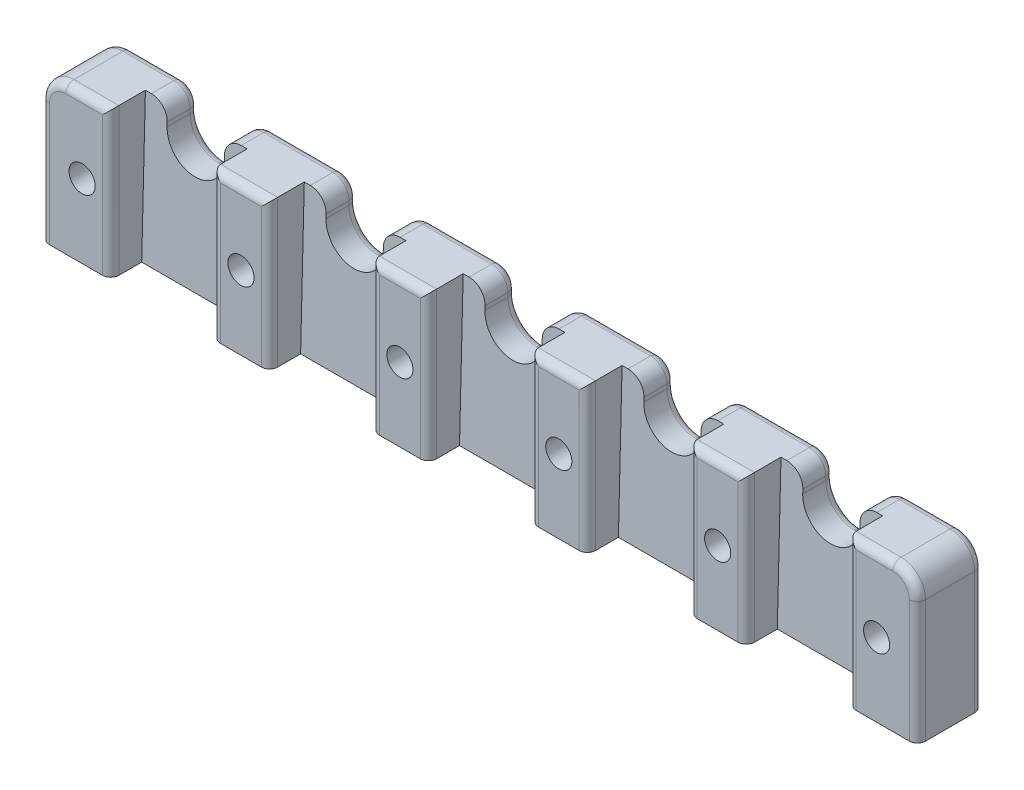
SolidWorks part; units mm, degrees
ref_plane "Front Plane" through (0, 0, 0) normal (0, 0, 1) x (1, 0, 0)
ref_plane "Top Plane" through (0, 0, 0) normal (0, 1, 0) x (1, 0, 0)
ref_plane "Right Plane" through (0, 0, 0) normal (1, 0, 0) x (0, 0, -1)
sketch "Sketch1" plane through (0, 0, 0) normal (0, 1, 0) x (1, 0, 0)
  line L0 (0, 0) -> (-0.0507, 0) construction
  line L1 (19.45, 0) -> (19.3993, 0) construction
  line L2 (-6.225, 10.725) -> (6.225, 10.725)
  line L3 (-6.225, 10.725) -> (-6.225, -10.725)
  line L4 (-6.225, -10.725) -> (6.225, -10.725)
  line L5 (6.225, 10.725) -> (6.225, -10.725)
  line L6 (-6.225, 10.725) -> (6.225, -10.725) construction
  line L7 (-6.225, -10.725) -> (6.225, 10.725) construction
  line L8 (13.225, 10.725) -> (13.225, -10.725)
  line L9 (13.225, 10.725) -> (25.675, 10.725)
  line L10 (25.675, 10.725) -> (25.675, -10.725)
  line L11 (13.225, -10.725) -> (25.675, -10.725)
  line L12 (38.9, 0) -> (38.8493, 0) construction
  line L13 (32.675, 10.725) -> (32.675, -10.725)
  line L14 (32.675, 10.725) -> (45.125, 10.725)
  line L15 (45.125, 10.725) -> (45.125, -10.725)
  line L16 (32.675, -10.725) -> (45.125, -10.725)
  line L17 (58.35, 0) -> (58.2993, 0) construction
  line L18 (52.125, 10.725) -> (52.125, -10.725)
  line L19 (52.125, 10.725) -> (64.575, 10.725)
  line L20 (64.575, 10.725) -> (64.575, -10.725)
  line L21 (52.125, -10.725) -> (64.575, -10.725)
  line L22 (77.8, 0) -> (77.7493, 0) construction
  line L23 (71.575, 10.725) -> (71.575, -10.725)
  line L24 (71.575, 10.725) -> (84.025, 10.725)
  line L25 (84.025, 10.725) -> (84.025, -10.725)
  line L26 (71.575, -10.725) -> (84.025, -10.725)
  line L27 (-19.225, -19.625) -> (-5.1, -19.625)
  line L28 (-9.225, 13.725) -> (87.025, 13.725)
  line L29 (-9.225, 13.725) -> (-9.225, -10.725)
  line L30 (-5.1, -13.725) -> (5.1, -13.725)
  line L31 (87.025, 13.725) -> (87.025, -10.725)
  line L32 (-9.225, 13.725) -> (87.025, -13.725) construction
  line L33 (-9.225, -13.725) -> (87.025, 13.725) construction
  line L34 (-19.225, -19.625) -> (-19.225, -10.725)
  line L35 (-19.225, -10.725) -> (-9.225, -10.725)
  line L36 (87.025, -10.725) -> (97.025, -10.725)
  line L37 (97.025, -10.725) -> (97.025, -19.625)
  line L38 (-5.1, -13.725) -> (-5.1, -19.625)
  line L39 (5.1, -13.725) -> (5.1, -19.625)
  line L40 (5.1, -19.625) -> (14.35, -19.625)
  line L41 (14.35, -19.625) -> (14.35, -13.725)
  line L42 (24.55, -13.725) -> (24.55, -19.625)
  line L43 (24.55, -19.625) -> (33.8, -19.625)
  line L44 (33.8, -19.625) -> (33.8, -13.725)
  line L45 (44, -13.725) -> (44, -19.625)
  line L46 (44, -19.625) -> (53.25, -19.625)
  line L47 (53.25, -19.625) -> (53.25, -13.725)
  line L48 (63.45, -13.725) -> (63.45, -19.625)
  line L49 (63.45, -19.625) -> (72.7, -19.625)
  line L50 (72.7, -19.625) -> (72.7, -13.725)
  line L51 (82.9, -13.725) -> (82.9, -19.625)
  line L52 (5.1, -19.625) -> (14.35, -19.625)
  line L53 (24.55, -19.625) -> (33.8, -19.625)
  line L54 (44, -19.625) -> (53.25, -19.625)
  line L55 (63.45, -19.625) -> (72.7, -19.625)
  line L56 (82.9, -19.625) -> (97.025, -19.625)
  line L57 (14.35, -13.725) -> (24.55, -13.725)
  line L58 (33.8, -13.725) -> (44, -13.725)
  line L59 (53.25, -13.725) -> (63.45, -13.725)
  line L60 (72.7, -13.725) -> (82.9, -13.725)
  line L61 (72.7, -13.725) -> (72.7, -19.625)
  line L62 (63.45, -19.625) -> (63.45, -13.725)
  line L63 (53.25, -13.725) -> (53.25, -19.625)
  line L64 (44, -19.625) -> (44, -13.725)
  line L65 (0, -10.725) -> (0, -17.5719) construction
  line L66 (19.45, -10.725) -> (19.45, -16.6206) construction
  line L67 (38.9, -10.725) -> (38.9, -17.5719) construction
  line L68 (58.35, -10.725) -> (58.35, -17.5719) construction
  line L69 (77.8, -10.725) -> (77.8, -17.5719) construction
  point P71 (0, -13.725)
  point P72 (19.45, -13.725)
  point P73 (38.9, -13.725)
  point P74 (58.35, -13.725)
  point P75 (77.8, -13.725)
  dimension "D1" = 12.45
  dimension "D2" = 21.45
  dimension "D4" = 3
  dimension "D5" = 3
  dimension "D6" = 5.9
  dimension "D7" = 10
  dimension "D8" = 10
  dimension "D9" = 10.2
  dimension "D10" = 10.2
  dimension "D11" = 10.2
  dimension "D12" = 10.2
  dimension "D13" = 10.2
  dimension "D3" = 5
extrude "Boss-Extrude1" add sketch "Sketch1" along normal blind 18 contours L50 L60 L51 L56 L37 L36 L31 L28 L29 L35 L34 L27 L38 L30 L39 L40 L41 L57 L42 L43 L44 L58 L45 L46 L47 L59 L48 L49 L2 L5 L4 L3 L11 L8 L9 L10 L16 L13 L14 L15 L21 L18 L19 L20 L26 L23
sketch "Sketch2" plane through (0, 18, 0) normal (0, 1, 0) x (1, 0, 0)
  line L0 (-9.225, 13.725) -> (-9.225, -10.725) construction
  line L1 (-19.225, -10.725) -> (-9.225, -10.725)
  line L2 (-19.225, -10.725) -> (-19.225, -7.725)
  line L3 (-19.225, -7.725) -> (-9.225, -7.725)
  line L4 (-9.225, -10.725) -> (-9.225, -7.725)
  line L5 (87.025, 13.725) -> (87.025, -10.725) construction
  line L6 (97.025, -10.725) -> (87.025, -10.725)
  line L7 (97.025, -10.725) -> (97.025, -7.725)
  line L8 (97.025, -7.725) -> (87.025, -7.725)
  line L9 (87.025, -10.725) -> (87.025, -7.725)
  dimension "D1" = 3
  dimension "D2" = 3
extrude "Boss-Extrude2" add sketch "Sketch2" against normal up to surface (18 mm away) up to face at (0, 0, 0)
sketch "Sketch4" plane through (0, 18, 0) normal (0, 1, 0) x (1, 0, 0)
  line L0 (-6.225, 10.725) -> (6.225, 10.725) construction
  line L1 (-3.5, 14.8177) -> (3.5, 14.8177)
  line L2 (-3.5, 14.8177) -> (-3.5, 6.6323)
  line L3 (-3.5, 6.6323) -> (3.5, 6.6323)
  line L4 (3.5, 14.8177) -> (3.5, 6.6323)
  line L5 (-3.5, 14.8177) -> (3.5, 6.6323) construction
  line L6 (-3.5, 6.6323) -> (3.5, 14.8177) construction
  line L7 (13.225, 10.725) -> (25.675, 10.725) construction
  line L8 (15.95, 15.2856) -> (22.95, 15.2856)
  line L9 (15.95, 15.2856) -> (15.95, 6.1644)
  line L10 (15.95, 6.1644) -> (22.95, 6.1644)
  line L11 (22.95, 15.2856) -> (22.95, 6.1644)
  line L12 (15.95, 15.2856) -> (22.95, 6.1644) construction
  line L13 (15.95, 6.1644) -> (22.95, 15.2856) construction
  line L14 (32.675, 10.725) -> (45.125, 10.725) construction
  line L15 (35.4, 17.4328) -> (42.4, 17.4328)
  line L16 (35.4, 17.4328) -> (35.4, 4.0172)
  line L17 (35.4, 4.0172) -> (42.4, 4.0172)
  line L18 (42.4, 17.4328) -> (42.4, 4.0172)
  line L19 (35.4, 17.4328) -> (42.4, 4.0172) construction
  line L20 (35.4, 4.0172) -> (42.4, 17.4328) construction
  line L21 (52.125, 10.725) -> (64.575, 10.725) construction
  line L22 (54.85, 15.7825) -> (61.85, 15.7825)
  line L23 (54.85, 15.7825) -> (54.85, 5.6675)
  line L24 (54.85, 5.6675) -> (61.85, 5.6675)
  line L25 (61.85, 15.7825) -> (61.85, 5.6675)
  line L26 (54.85, 15.7825) -> (61.85, 5.6675) construction
  line L27 (54.85, 5.6675) -> (61.85, 15.7825) construction
  line L28 (71.575, 10.725) -> (84.025, 10.725) construction
  line L29 (74.3, 15.0129) -> (81.3, 15.0129)
  line L30 (74.3, 15.0129) -> (74.3, 6.4371)
  line L31 (74.3, 6.4371) -> (81.3, 6.4371)
  line L32 (81.3, 15.0129) -> (81.3, 6.4371)
  line L33 (74.3, 15.0129) -> (81.3, 6.4371) construction
  line L34 (74.3, 6.4371) -> (81.3, 15.0129) construction
  point P0 (0, 10.725)
  point P7 (19.45, 10.725)
  point P14 (38.9, 10.725)
  point P21 (58.35, 10.725)
  point P28 (77.8, 10.725)
  dimension "D1" = 7
  dimension "D2" = 7
  dimension "D3" = 7
  dimension "D4" = 7
  dimension "D5" = 7
extrude "Cut-Extrude2" cut sketch "Sketch4" against normal blind 6
fillet "Fillet3" radius 3.5 10 edges at (81.3, 12, -12.225) (74.3, 12, -12.225) (54.85, 12, -12.225) (61.85, 12, -12.225) (42.4, 12, -12.225) (35.4, 12, -12.225) (15.95, 12, -12.225) (22.95, 12, -12.225) (3.5, 12, -12.225) (-3.5, 12, -12.225)
fillet "Fillet4" radius 2 10 edges at (35.4, 18, -12.225) (54.85, 18, -12.225) (74.3, 18, -12.225) (81.3, 18, -12.225) (61.85, 18, -12.225) (42.4, 18, -12.225) (22.95, 18, -12.225) (15.95, 18, -12.225) (3.5, 18, -12.225) (-3.5, 18, -12.225)
sketch "Sketch5" plane through (0, 0, 19.625) normal (0, 0, 1) x (1, 0, 0)
  line L0 (-19.225, 9) -> (97.025, 9) construction
  line L1 (-19.225, 18) -> (-19.225, 0) construction
  line L2 (97.025, 18) -> (97.025, 0) construction
  line L3 (5.1, 9) -> (14.35, 9) construction
  line L4 (5.1, 18) -> (5.1, 0) construction
  line L5 (14.35, 18) -> (14.35, 0) construction
  line L6 (24.55, 9) -> (33.8, 9) construction
  line L7 (24.55, 18) -> (24.55, 0) construction
  line L8 (33.8, 18) -> (33.8, 0) construction
  line L9 (44, 9) -> (53.25, 9) construction
  line L10 (44, 18) -> (44, 0) construction
  line L11 (53.25, 18) -> (53.25, 0) construction
  line L12 (63.45, 9) -> (72.7, 9) construction
  line L13 (63.45, 18) -> (63.45, 0) construction
  line L14 (72.7, 18) -> (72.7, 0) construction
  line L15 (-5.1, 18) -> (-5.1, 0) construction
  line L16 (82.9, 18) -> (82.9, 0) construction
  circle A0 centre (9.725, 9) radius 1.6
  circle A1 centre (29.175, 9) radius 1.6
  circle A2 centre (48.625, 9) radius 1.6
  circle A3 centre (68.075, 9) radius 1.6
  circle A4 centre (87.53, 9) radius 1.6
  circle A5 centre (-9.73, 9) radius 1.6
  dimension "D1" = 3.2
  dimension "D2" = 3.2
  dimension "D3" = 3.2
  dimension "D4" = 3.2
  dimension "D5" = 3.2
  dimension "D6" = 3.2
  dimension "D7" = 4.63
  dimension "D8" = 4.63
extrude "Cut-Extrude3" cut sketch "Sketch5" against normal through all
sketch "Sketch7" plane through (0, 0, -13.725) normal (0, 0, -1) x (-1, 0, 0)
  line L0 (-87.53, 9) -> (-92.53, 9) construction
  line L1 (9.73, 9) -> (14.73, 9) construction
  line L2 (-92.53, 9) -> (-92.53, -2.9346)
  line L3 (-92.53, -2.9346) -> (-102.871, -2.9346)
  line L4 (-102.871, -2.9346) -> (-102.871, 21.3195)
  line L5 (-102.871, 21.3195) -> (-92.53, 21.3195)
  line L6 (-92.53, 21.3195) -> (-92.53, 9)
  line L7 (14.73, 9) -> (14.73, -3.3373)
  line L8 (14.73, -3.3373) -> (26.9404, -3.3373)
  line L9 (26.9404, -3.3373) -> (26.9404, 20.1807)
  line L10 (26.9404, 20.1807) -> (14.73, 20.1807)
  line L11 (14.73, 20.1807) -> (14.73, 9)
  dimension "D1" = 5
  dimension "D2" = 5
extrude "Cut-Extrude4" cut sketch "Sketch7" against normal through all
sketch "Sketch10" plane through (0, 0, 7.725) normal (0, 0, -1) x (-1, 0, 0)
  line L0 (-83.3, 18) -> (-87.025, 18) construction
  line L1 (-85.1625, 18) -> (-92.53, 18)
  line L2 (-85.1625, 18) -> (-85.1625, 0)
  line L3 (-85.1625, 0) -> (-92.53, 0)
  line L4 (-92.53, 18) -> (-92.53, 0)
  line L5 (9.225, 18) -> (5.5, 18) construction
  line L6 (14.73, 0) -> (7.3625, 0)
  line L7 (14.73, 0) -> (14.73, 18)
  line L8 (14.73, 18) -> (7.3625, 18)
  line L9 (7.3625, 0) -> (7.3625, 18)
  circle A0 centre (-87.53, 9) radius 1.6
  circle A1 centre (9.73, 9) radius 1.6
extrude "Boss-Extrude4" add sketch "Sketch10" along normal up to surface (21.45 mm away) up to face at (38.9, 14.5091, -13.725)
fillet "Fillet6" radius 3 2 edges at (-14.73, 18, 2.95) (92.53, 18, 2.95)
sketch "Sketch11" plane through (0, 18, 0) normal (0, 1, 0) x (1, 0, 0)
  line L1 (-18.1321, 4.725) -> (96.0074, 4.725)
  line L2 (-18.1321, 4.725) -> (-18.1321, 5.725)
  line L3 (-18.1321, 5.725) -> (96.0074, 5.725)
  line L4 (96.0074, 4.725) -> (96.0074, 5.725)
  line L5 (-11.73, 13.725) -> (-5.5, 13.725) construction
  dimension "D1" = 8
  dimension "D2" = 1
extrude "Cut-Extrude5" cut sketch "Sketch11" against normal through all
chamfer "Chamfer2" distance 1 angle 45 44 edges at (-9.915, 0, 19.625) (-14.73, 0, 7.45) (68.075, 0, 19.625) (63.45, 0, 16.675) (58.35, 0, 13.725) (53.25, 0, 16.675) (48.625, 0, 19.625) (44, 0, 16.675) (38.9, 0, 13.725) (33.8, 0, 16.675) (29.175, 0, 19.625) (24.55, 0, 16.675) (19.45, 0, 13.725) (14.35, 0, 16.675) (9.725, 0, 19.625) (5.1, 0, 16.675) (0, 0, 13.725) (-5.1, 0, 16.675) (92.53, 0, 7.45) (-6.225, 0, 3) (6.225, 0, 3) (25.675, 0, 3) (87.715, 0, 19.625) (13.225, 0, 3) (45.125, 0, 3) (32.675, 0, 3) (64.575, 0, 3) (52.125, 0, 3) (84.025, 0, 3) (71.575, 0, 3) (82.9, 0, 16.675) (77.8, 0, 13.725) (72.7, 0, 16.675) (77.8, 0, 10.725) (9.725, 0, -4.725) (88.2775, 0, -4.725) (68.075, 0, -4.725) (48.625, 0, -4.725) (29.175, 0, -4.725) (-10.4775, 0, -4.725) (58.35, 0, 10.725) (38.9, 0, 10.725) (19.45, 0, 10.725) (0, 0, 10.725)
fillet "Fillet7" radius 1 20 edges at (91.6513, 17.1213, -4.725) (71.575, 9.5, -4.725) (52.125, 9.5, -4.725) (32.675, 9.5, -4.725) (13.225, 9.5, -4.725) (6.225, 9.5, -4.725) (84.025, 9.5, -4.725) (64.575, 9.5, -4.725) (45.125, 9.5, -4.725) (25.675, 9.5, -4.725) (-6.225, 9.5, -4.725) (-14.73, 8, -4.725) (-13.8513, 17.1213, -4.725) (9.725, 18, -4.725) (86.7775, 18, -4.725) (68.075, 18, -4.725) (48.625, 18, -4.725) (29.175, 18, -4.725) (-8.9775, 18, -4.725) (92.53, 8, -4.725)
fillet "Fillet8" radius 1 15 edges at (92.53, 7.5, -5.725) (91.6513, 17.1213, -5.725) (-14.73, 7.5, -5.725) (-13.8513, 17.1213, -5.725) (-8.9775, 18, -5.725) (84.025, 9, -5.725) (64.575, 9, -5.725) (71.575, 9, -5.725) (52.125, 9, -5.725) (45.125, 9, -5.725) (25.675, 9, -5.725) (32.675, 9, -5.725) (13.225, 9, -5.725) (6.225, 9, -5.725) (-6.225, 9, -5.725)
fillet "Fillet9" radius 1 40 edges at (-2.4749, 13.0251, -13.725) (2.4749, 13.0251, -13.725) (4.0858, 17.4142, -13.725) (9.725, 18, -13.725) (15.3642, 17.4142, -13.725) (16.9751, 13.0251, -13.725) (21.9249, 13.0251, -13.725) (23.5358, 17.4142, -13.725) (29.175, 18, -13.725) (34.8142, 17.4142, -13.725) (36.4251, 13.0251, -13.725) (41.3749, 13.0251, -13.725) (42.9858, 17.4142, -13.725) (48.625, 18, -13.725) (54.2642, 17.4142, -13.725) (55.8751, 13.0251, -13.725) (60.8249, 13.0251, -13.725) (62.4358, 17.4142, -13.725) (68.075, 18, -13.725) (73.7142, 17.4142, -13.725) (75.3251, 13.0251, -13.725) (80.2749, 13.0251, -13.725) (81.8858, 17.4142, -13.725) (86.415, 18, -13.725) (91.6513, 17.1213, -13.725) (92.53, 7.5, -13.725) (81.3, 15.75, -13.725) (74.3, 15.75, -13.725) (61.85, 15.75, -13.725) (54.85, 15.75, -13.725) (42.4, 15.75, -13.725) (35.4, 15.75, -13.725) (22.95, 15.75, -13.725) (15.95, 15.75, -13.725) (3.5, 15.75, -13.725) (-3.5, 15.75, -13.725) (-14.73, 7.5, -13.725) (-13.8513, 17.1213, -13.725) (-8.615, 18, -13.725) (-4.0858, 17.4142, -13.725)
sketch "Sketch13" plane through (0, 0, 19.625) normal (0, 0, 1) x (1, 0, 0)
  circle A0 centre (-9.73, 9) radius 2.05
  circle A1 centre (9.725, 9) radius 2.05
  circle A2 centre (29.175, 9) radius 2.05
  circle A3 centre (48.625, 9) radius 2.05
  circle A4 centre (68.075, 9) radius 2.05
  circle A5 centre (87.53, 9) radius 2.05
  dimension "D1" = 4.1
  dimension "D2" = 4.1
  dimension "D3" = 4.1
  dimension "D4" = 4.1
  dimension "D5" = 4.1
  dimension "D6" = 4.1
extrude "Cut-Extrude6" cut sketch "Sketch13" against normal blind 8
sketch "Sketch14" plane through (0, 0, -4.725) normal (0, 0, -1) x (-1, 0, 0)
  circle A0 centre (-87.53, 9) radius 2.05
  circle A1 centre (-68.075, 9) radius 2.05
  circle A2 centre (-48.625, 9) radius 2.05
  circle A3 centre (-29.175, 9) radius 2.05
  circle A4 centre (-9.725, 9) radius 2.05
  circle A5 centre (9.73, 9) radius 2.05
  dimension "D1" = 4.1
  dimension "D2" = 4.1
  dimension "D3" = 4.1
  dimension "D4" = 4.1
  dimension "D5" = 4.1
  dimension "D6" = 4.1
extrude "Cut-Extrude7" cut sketch "Sketch14" against normal blind 10
sketch "Sketch15" plane through (0, 0, 0) normal (0, -1, 0) x (1, 0, 0)
  line L1 (-19.0841, 27.9994) -> (94.9162, 27.9994)
  line L2 (-19.0841, 27.9994) -> (-19.0841, -5.1442)
  line L3 (-19.0841, -5.1442) -> (94.9162, -5.1442)
  line L4 (94.9162, 27.9994) -> (94.9162, -5.1442)
extrude "Cut-Extrude8" cut sketch "Sketch15" against normal through all
sketch "Sketch16" plane through (0, 0, -13.725) normal (0, 0, -1) x (-1, 0, 0)
  circle A0 centre (-87.53, 9) radius 3
  circle A1 centre (-68.075, 9) radius 3
  circle A2 centre (-48.625, 9) radius 3
  circle A3 centre (-29.175, 9) radius 3
  circle A4 centre (-9.725, 9) radius 3
  circle A5 centre (9.73, 9) radius 3
extrude "Cut-Extrude9" cut sketch "Sketch16" against normal blind 2
chamfer "Chamfer3" distance 0.5 angle 45 6 edges at (84.53, 9, -13.725) (65.075, 9, -13.725) (45.625, 9, -13.725) (26.175, 9, -13.725) (6.725, 9, -13.725) (-12.73, 9, -13.725)
sketch "Sketch17" plane through (6.225, 0, 0) normal (-1, 0, 0) x (0, 0, 1)
  line L0 (-10.725, 18) -> (-10.725, 0)
  line L1 (-10.725, 0) -> (-9.525, 0)
  line L2 (-10.725, 0) -> (-6.725, 0) construction
  line L3 (-9.525, 0) -> (-9.975, 18)
  line L4 (-10.725, 18) -> (-6.725, 18) construction
  line L5 (-9.975, 18) -> (-10.725, 18)
  dimension "D1" = 1.2
  dimension "D2" = 0.75
extrude "Boss-Extrude5" add sketch "Sketch17" against normal up to surface and the other way blind 13 up to face at (84.025, 9, -8.725)
sketch "Sketch18" plane through (0, 0, -13.725) normal (0, 0, -1) x (-1, 0, 0)
  line L44 (-72.3, 18) -> (-83.3, 18)
  line L45 (-81.3, 16) -> (-81.3, 15.5)
  line L46 (-74.3, 15.5) -> (-74.3, 16)
  line L47 (-72.3, 18) -> (-83.3, 18)
  line L48 (-81.3, 16) -> (-81.3, 15.5)
  line L49 (-74.3, 15.5) -> (-74.3, 16)
  line L53 (-52.85, 18) -> (-63.85, 18)
  line L54 (-61.85, 16) -> (-61.85, 15.5)
  line L55 (-54.85, 15.5) -> (-54.85, 16)
  line L56 (-52.85, 18) -> (-63.85, 18)
  line L57 (-61.85, 16) -> (-61.85, 15.5)
  line L58 (-54.85, 15.5) -> (-54.85, 16)
  line L62 (-33.4, 18) -> (-44.4, 18)
  line L63 (-42.4, 16) -> (-42.4, 15.5)
  line L64 (-35.4, 15.5) -> (-35.4, 16)
  line L65 (-33.4, 18) -> (-44.4, 18)
  line L66 (-42.4, 16) -> (-42.4, 15.5)
  line L67 (-35.4, 15.5) -> (-35.4, 16)
  line L71 (-22.95, 16) -> (-22.95, 15.5)
  line L72 (-15.95, 15.5) -> (-15.95, 16)
  line L73 (-13.95, 18) -> (-24.95, 18)
  line L74 (-22.95, 16) -> (-22.95, 15.5)
  line L75 (-15.95, 15.5) -> (-15.95, 16)
  line L76 (-13.95, 18) -> (-24.95, 18)
  line L80 (-3.5, 16) -> (-3.5, 15.5)
  line L81 (3.5, 15.5) -> (3.5, 16)
  line L82 (5.5, 18) -> (-5.5, 18)
  line L83 (-3.5, 16) -> (-3.5, 15.5)
  line L84 (3.5, 15.5) -> (3.5, 16)
  line L85 (5.5, 18) -> (-5.5, 18)
  arc A52 (-72.3, 18) -> (-74.3, 16) centre (-72.3, 16) ccw
  arc A53 (-81.3, 16) -> (-83.3, 18) centre (-83.3, 16) ccw
  arc A54 (-81.3, 15.5) -> (-77.8, 12) centre (-77.8, 15.5) ccw
  arc A55 (-77.8, 12) -> (-74.3, 15.5) centre (-77.8, 15.5) ccw
  arc A56 (-72.3, 18) -> (-74.3, 16) centre (-72.3, 16) ccw
  arc A57 (-81.3, 16) -> (-83.3, 18) centre (-83.3, 16) ccw
  arc A58 (-81.3, 15.5) -> (-77.8, 12) centre (-77.8, 15.5) ccw
  arc A59 (-77.8, 12) -> (-74.3, 15.5) centre (-77.8, 15.5) ccw
  arc A64 (-52.85, 18) -> (-54.85, 16) centre (-52.85, 16) ccw
  arc A65 (-61.85, 16) -> (-63.85, 18) centre (-63.85, 16) ccw
  arc A66 (-61.85, 15.5) -> (-58.35, 12) centre (-58.35, 15.5) ccw
  arc A67 (-58.35, 12) -> (-54.85, 15.5) centre (-58.35, 15.5) ccw
  arc A68 (-52.85, 18) -> (-54.85, 16) centre (-52.85, 16) ccw
  arc A69 (-61.85, 16) -> (-63.85, 18) centre (-63.85, 16) ccw
  arc A70 (-61.85, 15.5) -> (-58.35, 12) centre (-58.35, 15.5) ccw
  arc A71 (-58.35, 12) -> (-54.85, 15.5) centre (-58.35, 15.5) ccw
  arc A76 (-33.4, 18) -> (-35.4, 16) centre (-33.4, 16) ccw
  arc A77 (-42.4, 16) -> (-44.4, 18) centre (-44.4, 16) ccw
  arc A78 (-42.4, 15.5) -> (-38.9, 12) centre (-38.9, 15.5) ccw
  arc A79 (-38.9, 12) -> (-35.4, 15.5) centre (-38.9, 15.5) ccw
  arc A80 (-33.4, 18) -> (-35.4, 16) centre (-33.4, 16) ccw
  arc A81 (-42.4, 16) -> (-44.4, 18) centre (-44.4, 16) ccw
  arc A82 (-42.4, 15.5) -> (-38.9, 12) centre (-38.9, 15.5) ccw
  arc A83 (-38.9, 12) -> (-35.4, 15.5) centre (-38.9, 15.5) ccw
  arc A88 (-22.95, 16) -> (-24.95, 18) centre (-24.95, 16) ccw
  arc A89 (-22.95, 15.5) -> (-19.45, 12) centre (-19.45, 15.5) ccw
  arc A90 (-19.45, 12) -> (-15.95, 15.5) centre (-19.45, 15.5) ccw
  arc A91 (-13.95, 18) -> (-15.95, 16) centre (-13.95, 16) ccw
  arc A92 (-22.95, 16) -> (-24.95, 18) centre (-24.95, 16) ccw
  arc A93 (-22.95, 15.5) -> (-19.45, 12) centre (-19.45, 15.5) ccw
  arc A94 (-19.45, 12) -> (-15.95, 15.5) centre (-19.45, 15.5) ccw
  arc A95 (-13.95, 18) -> (-15.95, 16) centre (-13.95, 16) ccw
  circle A98 centre (-68.075, 9) radius 1.6
  circle A99 centre (-68.075, 9) radius 1.6
  arc A100 (-3.5, 16) -> (-5.5, 18) centre (-5.5, 16) ccw
  arc A101 (-3.5, 15.5) -> (0, 12) centre (0, 15.5) ccw
  arc A102 (0, 12) -> (3.5, 15.5) centre (0, 15.5) ccw
  arc A103 (5.5, 18) -> (3.5, 16) centre (5.5, 16) ccw
  arc A104 (-3.5, 16) -> (-5.5, 18) centre (-5.5, 16) ccw
  arc A105 (-3.5, 15.5) -> (0, 12) centre (0, 15.5) ccw
  arc A106 (0, 12) -> (3.5, 15.5) centre (0, 15.5) ccw
  arc A107 (5.5, 18) -> (3.5, 16) centre (5.5, 16) ccw
  circle A109 centre (-48.625, 9) radius 1.6
  circle A110 centre (-48.625, 9) radius 1.6
  circle A112 centre (-29.175, 9) radius 1.6
  circle A113 centre (-29.175, 9) radius 1.6
  circle A115 centre (-9.725, 9) radius 1.6
  circle A116 centre (-9.725, 9) radius 1.6
  dimension "D1" = 0
  dimension "D2" = 0
  dimension "D3" = 0
  dimension "D4" = 0
  dimension "D5" = 0
  dimension "D6" = 0
  dimension "D7" = 0
  dimension "D8" = 0
  dimension "D9" = 0
extrude "Cut-Extrude10" cut sketch "Sketch18" against normal blind 10
